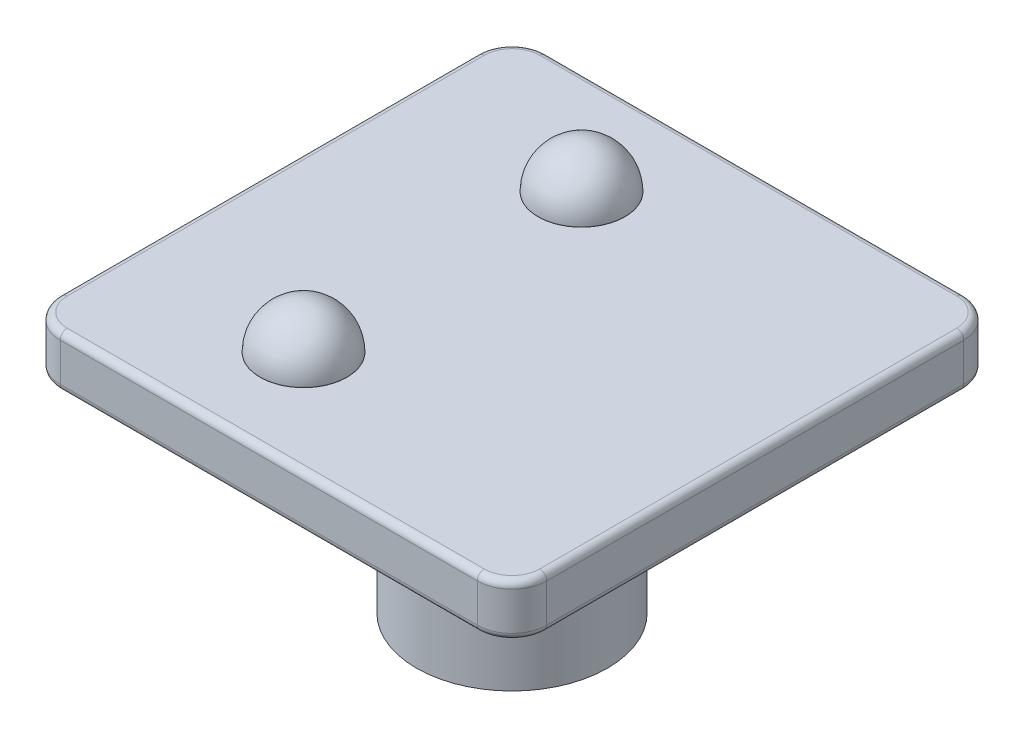
SolidWorks part; units mm, degrees
ref_plane "Front Plane" through (0, 0, 0) normal (0, 0, 1) x (1, 0, 0)
ref_plane "Top Plane" through (0, 0, 0) normal (0, 1, 0) x (1, 0, 0)
ref_plane "Right Plane" through (0, 0, 0) normal (1, 0, 0) x (0, 0, -1)
sketch "Sketch1" plane through (0, 0, 0) normal (0, 1, 0) x (1, 0, 0)
  line L1 (-7.3247, 4.3967) -> (4.6753, 4.3967)
  line L2 (-8.3247, 3.3967) -> (-8.3247, -8.6033)
  line L3 (-7.3247, -9.6033) -> (4.6753, -9.6033)
  line L4 (5.6753, 3.3967) -> (5.6753, -8.6033)
  arc A0 (-8.3247, -8.6033) -> (-7.3247, -9.6033) centre (-7.3247, -8.6033) ccw
  arc A1 (4.6753, -9.6033) -> (5.6753, -8.6033) centre (4.6753, -8.6033) ccw
  arc A2 (4.6753, 4.3967) -> (5.6753, 3.3967) centre (4.6753, 3.3967) cw
  arc A3 (-7.3247, 4.3967) -> (-8.3247, 3.3967) centre (-7.3247, 3.3967) ccw
  point P8 (5.6753, -9.6033)
  point P11 (5.6753, 4.3967)
  point P14 (-8.3247, 4.3967)
  dimension "D3" = 1
  dimension "D1" = 14
  dimension "D2" = 14
extrude "Boss-Extrude1" add sketch "Sketch1" along normal blind 1.5
sketch "Sketch2" plane through (0, 0, 0) normal (0, -1, 0) x (1, 0, 0)
  line L0 (-7.3247, 9.6033) -> (4.6753, 9.6033) construction
  line L1 (5.6753, 8.6033) -> (5.6753, -3.3967) construction
  line L2 (-1.3247, -4.3967) -> (-1.3247, 9.6033) construction
  line L3 (-8.3247, 2.6033) -> (5.6753, 2.6033) construction
  line L4 (-8.3247, -3.3967) -> (-8.3247, 8.6033) construction
  circle A0 centre (-1.3247, 2.6033) radius 2.75
  dimension "D1" = 7
  dimension "D2" = 7
extrude "Boss-Extrude2" add sketch "Sketch2" along normal blind 6
sketch "Sketch3" plane through (0, -6, 0) normal (0, -1, 0) x (1, 0, 0)
  line L0 (-1.3247, 5.3533) -> (-1.3247, -0.1467) construction
  line L1 (-3.3247, 3.1533) -> (0.6753, 3.1533)
  line L2 (-3.3247, 3.1533) -> (-3.3247, 2.0533)
  line L3 (-3.3247, 2.0533) -> (0.6753, 2.0533)
  line L4 (0.6753, 3.1533) -> (0.6753, 2.0533)
  line L5 (-1.8747, 4.6033) -> (-0.7747, 4.6033)
  line L6 (-1.8747, 4.6033) -> (-1.8747, 0.6033)
  line L7 (-1.8747, 0.6033) -> (-0.7747, 0.6033)
  line L8 (-0.7747, 4.6033) -> (-0.7747, 0.6033)
  line L9 (-4.0747, 2.6033) -> (1.4253, 2.6033) construction
  circle A3 centre (-1.3247, 2.6033) radius 2.75 construction
  circle A4 centre (-1.3247, 2.6033) radius 2.75 construction
  dimension "D7" = 0.55
  dimension "D1" = 4
  dimension "D2" = 1.1
  dimension "D3" = 1.1
  dimension "D4" = 4
  dimension "D8" = 0.55
extrude "Cut-Extrude1" cut sketch "Sketch3" against normal blind 6 contours L8 L5 L6 L1 | L1 L8 L3 L4 | L8 L1 L6 L3 | L6 L1 L2 L3 | L8 L3 L6 L7 region at (-2.5997, -6, 2.6033) region at (-1.3247, -6, 3.8783) region at (-1.3247, -6, 2.6033) region at (-0.0497, -6, 2.6033) region at (-1.3247, -6, 1.3283)
chamfer "Chamfer1" distance 0.3 angle 45 12 edges at (-1.3247, -6, 0.6033) (-1.8747, -6, 1.3283) (-2.5997, -6, 2.0533) (-3.3247, -6, 2.6033) (-2.5997, -6, 3.1533) (-0.7747, -6, 1.3283) (-0.0497, -6, 2.0533) (0.6753, -6, 2.6033) (-0.0497, -6, 3.1533) (-0.7747, -6, 3.8783) (-1.3247, -6, 4.6033) (-1.8747, -6, 3.8783)
fillet "Fillet1" radius 1 1 edges at (-1.3247, 0, -0.1467)
sketch "Sketch4" plane through (0, 1.5, 0) normal (0, 1, 0) x (1, 0, 0)
  line L0 (-1.3247, 4.3967) -> (-1.3247, -9.6033) construction
  line L1 (4.6753, 4.3967) -> (-7.3247, 4.3967) construction
  line L2 (-7.3247, -9.6033) -> (4.6753, -9.6033) construction
  line L3 (5.6753, -2.6033) -> (-8.3247, -2.6033) construction
  line L4 (-8.3247, 3.3967) -> (-8.3247, -8.6033) construction
  line L5 (5.6753, -8.6033) -> (5.6753, 3.3967) construction
  line L6 (-3.3247, 4.3967) -> (-3.3247, -9.6033) construction
  line L7 (0.6753, 4.3967) -> (0.6753, -9.6033) construction
  line L8 (-8.3247, 1.3967) -> (5.6753, 1.3967) construction
  line L9 (5.6753, -6.6033) -> (-8.3247, -6.6033) construction
  circle A0 centre (-3.3247, 1.3967) radius 1.25
  circle A3 centre (-3.3247, -6.6033) radius 1.25
  dimension "D1" = 4
  dimension "D2" = 4
  dimension "D3" = 2
  dimension "D4" = 2
extrude "Boss-Extrude3" add sketch "Sketch4" along normal blind 0.01
dome "Dome1" faces to dome 1 distance 1.25 reverse direction no elliptical dome no face at (-3.3247, 1.51, -0.1467) parameters "D1"=1.25
dome "Dome5" faces to dome 1 distance 1.25 reverse direction no elliptical dome no face at (-3.3247, 1.51, 7.8533) parameters "D1"=1.25
fillet "Fillet3" radius 0.2 16 edges at (5.3824, 1.5, -4.1038) (5.6753, 1.5, 2.6033) (5.3824, 1.5, 9.3104) (-1.3247, 1.5, 9.6033) (-8.0318, 1.5, 9.3104) (-8.0318, 1.5, -4.1038) (-8.3247, 1.5, 2.6033) (-1.3247, 1.5, -4.3967) (5.3824, 0, 9.3104) (5.6753, 0, 2.6033) (5.3824, 0, -4.1038) (-1.3247, 0, -4.3967) (-8.0318, 0, -4.1038) (-8.3247, 0, 2.6033) (-8.0318, 0, 9.3104) (-1.3247, 0, 9.6033)
